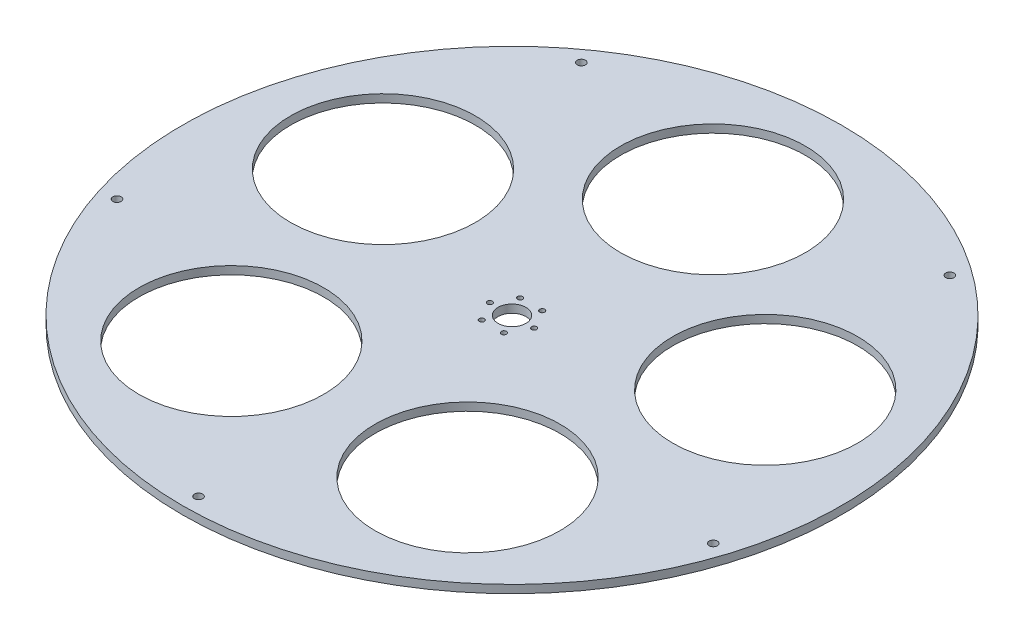
SolidWorks part; units mm, degrees
material "PC High Viscosity"
ref_plane "Front Plane" through (0, 0, 0) normal (0, 0, 1) x (1, 0, 0)
ref_plane "Top Plane" through (0, 0, 0) normal (0, 1, 0) x (1, 0, 0)
ref_plane "Right Plane" through (0, 0, 0) normal (1, 0, 0) x (0, 0, -1)
sketch "Sketch1" plane through (0, 0, 0) normal (0, 1, 0) x (1, 0, 0)
  circle A0 centre (0, 0) radius 260.35
  circle A1 centre (0, 158.75) radius 73.025
  circle A2 centre (150.9802, 49.0564) radius 73.025
  circle A3 centre (93.3109, -128.4314) radius 73.025
  circle A4 centre (-93.3109, -128.4314) radius 73.025
  circle A5 centre (-150.9802, 49.0564) radius 73.025
  point P15 (0, 0)
  dimension "D1" = 520.7
  dimension "D2" = 146.05
  dimension "D3" = 158.75
  dimension "D4" = 5
extrude "Boss-Extrude1" add sketch "Sketch1" along normal blind 6.35
sketch "Sketch3" plane through (-5.1845, 6.35, -2.4486) normal (0, 1, 0) x (1, 0, 0)
  circle A0 centre (5.1845, -2.4486) radius 11
  circle A1 centre (5.1845, -2.4486) radius 260.35 construction
  dimension "D1" = 22
extrude "Cut-Extrude1" cut sketch "Sketch3" against normal through all
hole_wizard "#10-32 Tapped Hole1" positions "Sketch5" profile "Sketch7" tap size "#10-32" standard "ANSI Inch" end condition through all
sketch "Sketch5" plane through (-5.1845, 6.35, -2.4486) normal (0, 1, 0) x (1, 0, 0)
  line L0 (5.1845, -2.4486) -> (-3.5467, 12.6744) construction
  line L2 (5.1845, -2.4486) -> (5.1845, 15.0139) construction
  circle A0 centre (5.1845, -2.4486) radius 17.4625
  point P0 (-3.5467, 12.6744)
  point P22 (13.9158, 12.6744)
  point P23 (22.647, -2.4486)
  point P24 (13.9158, -17.5715)
  point P25 (-3.5467, -17.5715)
  point P26 (-12.278, -2.4486)
  dimension "D1" = 34.925
  dimension "D2" = 30
  dimension "D3" = 6
sketch "Sketch7" plane through (-8.7313, 6.35, -15.123) normal (1, 0, 0) x (0, 0, 1)
  line L0 (0, 0) -> (0, 6.35)
  line L1 (0, 6.35) -> (2.0193, 6.35)
  line L2 (2.0193, 6.35) -> (2.0193, 0)
  line L5 (2.0193, 0) -> (0, 0)
  line L11 (0, -6.35) -> (0, 107.95) construction
  dimension "Thru Tap Drill Dia." = 4.0386
  dimension "Thru Tap Drill Depth" = 6.35
cosmetic thread "Hole Thread1" parameters "D2"=4.826
cosmetic thread "Hole Thread2" parameters "D2"=4.826
cosmetic thread "Hole Thread3" parameters "D2"=4.826
cosmetic thread "Hole Thread4" parameters "D2"=4.826
cosmetic thread "Hole Thread5" parameters "D2"=4.826
cosmetic thread "Hole Thread6" parameters "D2"=4.826
sketch "Sketch8" plane through (0, 6.35, 0) normal (0, 1, 0) x (1, 0, 0)
  circle A0 centre (0, -247.65) radius 3.2512
  circle A1 centre (-235.5291, -76.5281) radius 3.2512
  circle A2 centre (-145.565, 200.3531) radius 3.2512
  circle A3 centre (145.565, 200.3531) radius 3.2512
  circle A4 centre (235.5291, -76.5281) radius 3.2512
  point P14 (0, 0)
  dimension "D2" = 6.5024
  dimension "D1" = 247.65
  dimension "D3" = 5
extrude "Cut-Extrude2" cut sketch "Sketch8" against normal through all
